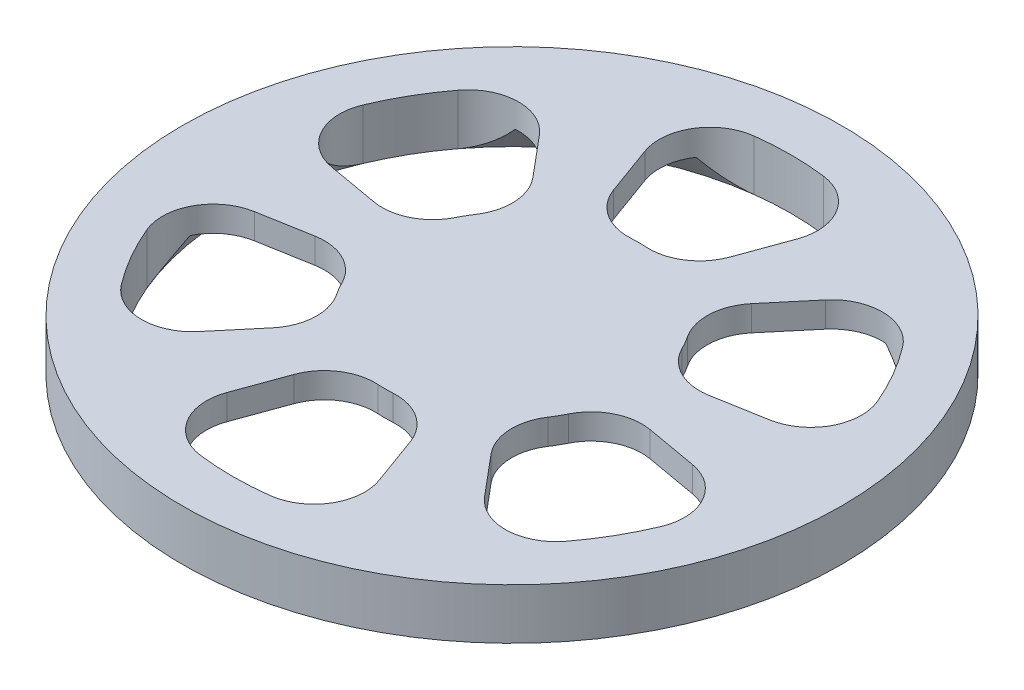
SolidWorks part; units mm, degrees
ref_plane "Front Plane" through (0, 0, 0) normal (0, 0, 1) x (1, 0, 0)
ref_plane "Top Plane" through (0, 0, 0) normal (0, 1, 0) x (1, 0, 0)
ref_plane "Right Plane" through (0, 0, 0) normal (1, 0, 0) x (0, 0, -1)
sketch "Sketch2" plane through (0, 0, 0) normal (0, 0, 1) x (1, 0, 0)
  line L0 (0, 0) -> (-65, 0)
  line L1 (-65, 0) -> (-65, -10)
  line L2 (-65, -10) -> (-55, -10)
  line L3 (-55, -10) -> (-52.1132, -5)
  line L4 (-52.1132, -5) -> (0, -5)
  line L5 (0, 0) -> (0, -5)
  point P4 (-49.6942, -20.81)
  dimension "D1" = 65
  dimension "D2" = 60
  dimension "D3" = 10
  dimension "D4" = 5
  dimension "D5" = 10
revolve "Revolve1" add sketch "Sketch2" angle 360 about L5
sketch "Sketch4" plane through (0, 0, 0) normal (0, 1, 0) x (1, 0, 0)
  line L0 (0, -25) -> (0, -65)
  line L1 (-8.5505, -23.4923) -> (-22.2313, -61.08)
  line L2 (8.5505, -23.4923) -> (22.2313, -61.08)
  circle A0 centre (0, 0) radius 25
  circle A1 centre (0, 0) radius 65 construction
  circle A2 centre (0, 0) radius 65
  circle A3 centre (0, 0) radius 55
  dimension "D1" = 50
  dimension "D4" = 10
  dimension "D2" = 20
  dimension "D3" = 20
extrude "Cut-Extrude1" cut sketch "Sketch4" against normal through all contours L1 A3 L0 A0 | L0 A3 L2 A0
pattern_circular "CirPattern1" count 6 over 360 about axis through (0, 0, 0) along (0, 1, 0) of "Cut-Extrude1"
fillet "Fillet1" radius 10 24 edges at (-54.1644, -5, 9.5506) (-35.3533, -5, 42.1324) (-16.0697, -2.5, 19.1511) (-24.6202, -2.5, 4.3412) (35.3533, -5, 42.1324) (54.1644, -5, 9.5506) (16.0697, -2.5, 19.1511) (54.1644, -5, -9.5506) (35.3533, -5, -42.1324) (16.0697, -2.5, -19.1511) (24.6202, -2.5, -4.3412) (-35.3533, -5, -42.1324) (-54.1644, -5, -9.5506) (-24.6202, -2.5, -4.3412) (-16.0697, -2.5, -19.1511) (18.8111, -5, -51.6831) (-18.8111, -5, -51.6831) (-8.5505, -2.5, -23.4923) (8.5505, -2.5, -23.4923) (24.6202, -2.5, 4.3412) (-18.8111, -5, 51.6831) (18.8111, -5, 51.6831) (8.5505, -2.5, 23.4923) (-8.5505, -2.5, 23.4923)
